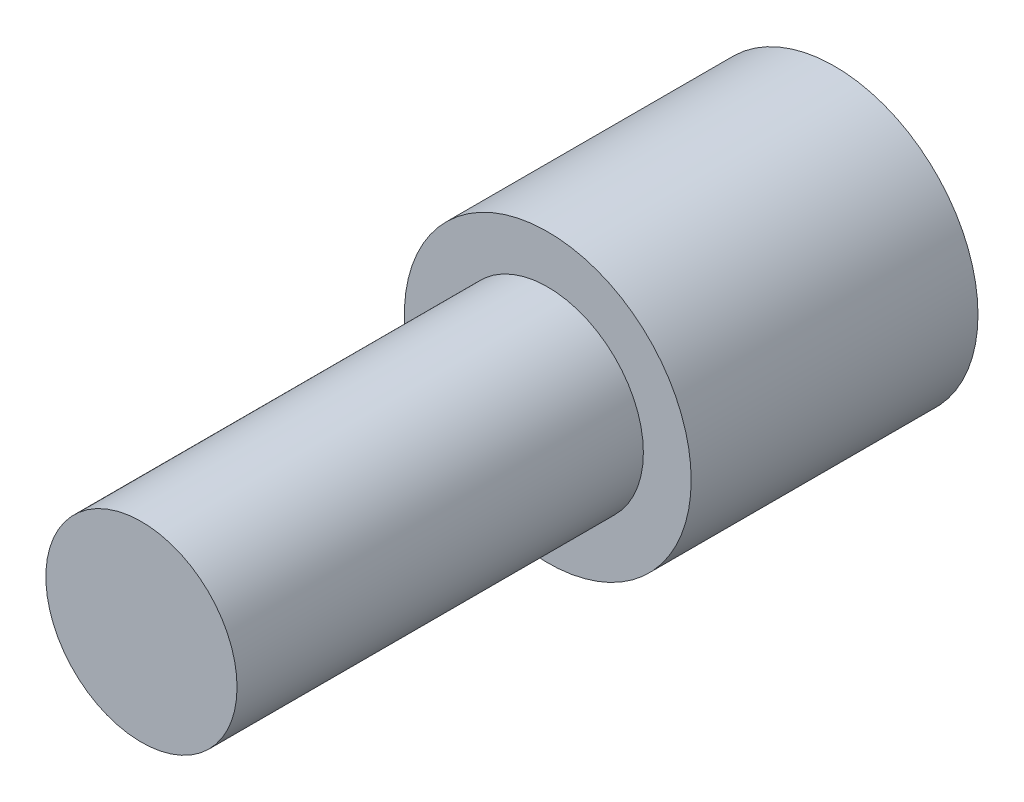
SolidWorks part; units mm, degrees
ref_plane "Front Plane" through (0, 0, 0) normal (0, 0, 1) x (1, 0, 0)
ref_plane "Top Plane" through (0, 0, 0) normal (0, 1, 0) x (1, 0, 0)
ref_plane "Right Plane" through (0, 0, 0) normal (1, 0, 0) x (0, 0, -1)
sketch "Sketch1" plane through (0, 0, 0) normal (0, 0, 1) x (1, 0, 0)
  circle A0 centre (0, 0) radius 4.1
  circle A1 centre (0, 0) radius 6
  dimension "D1" = 8.2
  dimension "D2" = 12
extrude "Boss-Extrude1" add sketch "Sketch1" along normal blind 10
sketch "Sketch2" plane through (0, 0, 10) normal (0, 0, 1) x (1, 0, 0)
  circle A0 centre (0, 0) radius 6
  circle A1 centre (0, 0) radius 6 construction
  dimension "D1" = 0
extrude "Boss-Extrude2" add sketch "Sketch2" along normal blind 2
sketch "Sketch3" plane through (0, 0, 12) normal (0, 0, 1) x (1, 0, 0)
  circle A0 centre (0, 0) radius 4
  dimension "D1" = 8
extrude "Boss-Extrude3" add sketch "Sketch3" along normal blind 17
